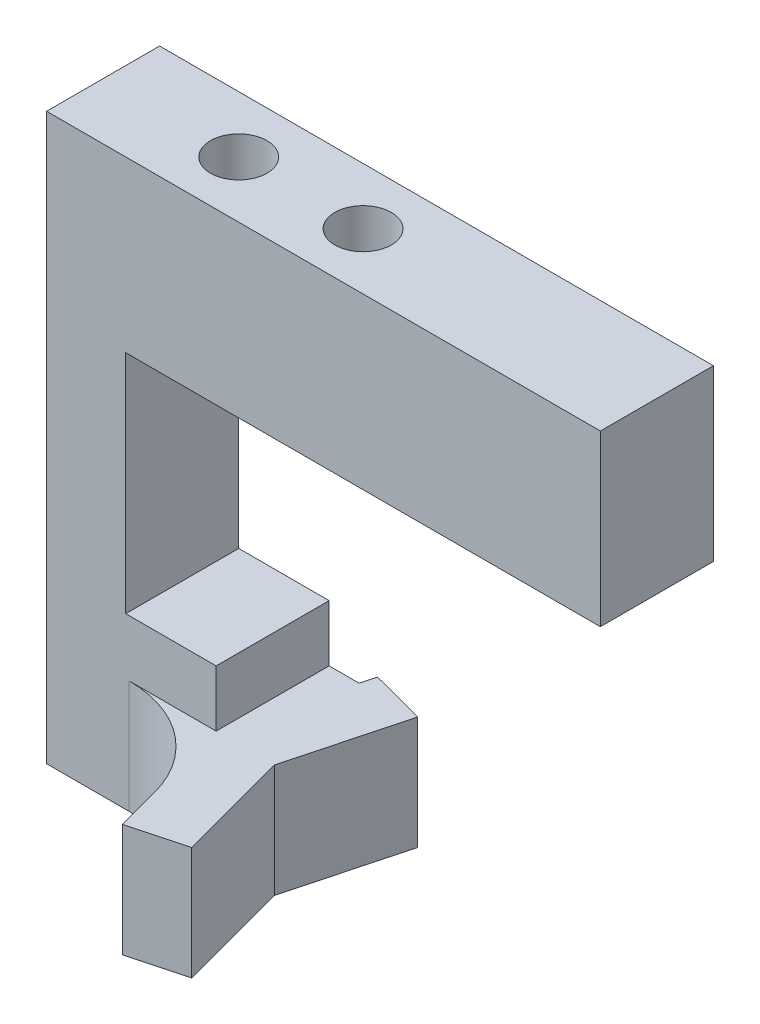
SolidWorks part; units mm, degrees
ref_plane "Front Plane" through (0, 0, 0) normal (0, 0, 1) x (1, 0, 0)
ref_plane "Top Plane" through (0, 0, 0) normal (0, 1, 0) x (1, 0, 0)
ref_plane "Right Plane" through (0, 0, 0) normal (1, 0, 0) x (0, 0, -1)
sketch "Sketch1" plane through (0, 0, 0) normal (0, 0, 1) x (1, 0, 0)
  line L0 (49, 0) -> (0, 0)
  line L1 (0, 0) -> (0, -50)
  line L2 (0, -50) -> (15, -50)
  line L3 (15, -50) -> (15, -15)
  line L4 (15, -15) -> (49, -15)
  line L5 (49, -15) -> (49, 0)
  dimension "D1" = 49
  dimension "D2" = 50
  dimension "D3" = 15
  dimension "D4" = 15
extrude "Boss-Extrude1" add sketch "Sketch1" along normal mid plane 10
sketch "Sketch2" plane through (0, -50, 0) normal (0, -1, 0) x (1, 0, 0)
  line L0 (18, -6.2846) -> (15, 5)
  line L1 (15, 5) -> (18, 16.2846)
  line L3 (15, 5) -> (25.3473, 5) construction
  line L4 (15, 5) -> (49, 5) construction
  line L5 (18, 16.2846) -> (22.8322, 15)
  line L6 (22.8322, 15) -> (20.1737, 5)
  line L7 (20.1737, 5) -> (22.8322, -5)
  line L8 (22.8322, -5) -> (18, -6.2846)
  line L9 (15, -5) -> (17.6585, -5)
  line L10 (15, -5) -> (49, -5) construction
  line M9 (15, -5) -> (15, 5)
  dimension "D1" = 5
  dimension "D2" = 3
extrude "Boss-Extrude2" add sketch "Sketch2" against normal blind 10 contours L8 L7 L6 L5 L1 L0 | L9 L0 M9 | L1 L3 L6 L5 region at (18.9511, -50, -0.3276) region at (15.8862, -50, -1.6667) region at (18.9511, -50, 10.3276)
fillet "Fillet1" radius 10 1 edges at (15, -45, 5)
sketch "Sketch3" plane through (0, 0, -5) normal (0, 0, -1) x (-1, 0, 0)
  line L0 (-7, 0) -> (-7, 22) construction
  line L1 (-15, -15) -> (-7, -15)
  line L2 (-15, -15) -> (-15, -35)
  line L3 (-15, -35) -> (-7, -35)
  line L4 (-7, -15) -> (-7, -35)
  dimension "D1" = 20
extrude "Cut-Extrude1" cut sketch "Sketch3" against normal through all
sketch "Sketch4" plane through (0, -15, 0) normal (0, -1, 0) x (1, 0, 0)
  circle A0 centre (23, 0) radius 2.5
  circle A1 centre (12, 0) radius 2.5
  dimension "D1" = 5
extrude "Cut-Extrude2" cut sketch "Sketch4" against normal through all
